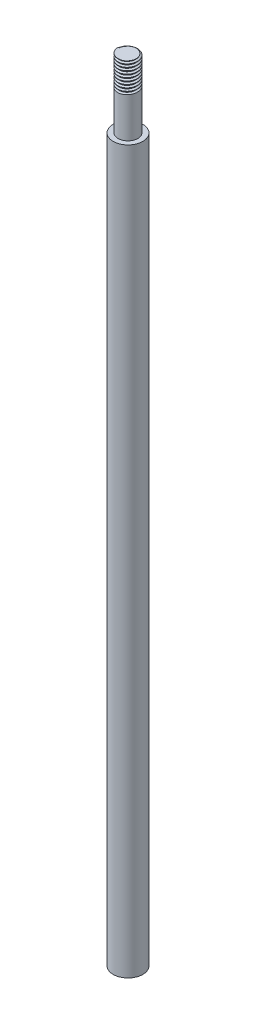
SolidWorks part; units mm, degrees
material "6061-T6 (SS)"
ref_plane "Front Plane" through (0, 0, 0) normal (0, 0, 1) x (1, 0, 0)
ref_plane "Top Plane" through (0, 0, 0) normal (0, 1, 0) x (1, 0, 0)
ref_plane "Right Plane" through (0, 0, 0) normal (1, 0, 0) x (0, 0, -1)
sketch "Sketch1" plane through (0, 0, 0) normal (0, 1, 0) x (1, 0, 0)
  circle A0 centre (0, 0) radius 5
extrude "Boss-Extrude1" add sketch "Sketch1" along normal blind 35
sketch "Sketch2" plane through (0, 0, 0) normal (0, -1, 0) x (1, 0, 0)
  line L0 (5, 0) -> (0, 0)
  circle A0 centre (0, 0) radius 5 construction
  circle A1 centre (0, 0) radius 7.5
  circle M1 centre (0, 0) radius 5
extrude "Boss-Extrude2" add sketch "Sketch2" along normal blind 365 contours A1 M1 | M1 region at (-7.2879, 0, 0) region at (-4.8586, 0, 0)
thread "Thread2" pitch 1.5 method cut trim with start face yes profile "Thread Profile3" start angle 0, offset 1, length 15, pitch 1.5, diameter 10
ref_plane "Plane3" through (-5, 36, 0) normal (0, 0, 1) x (-1, 0, 0)
sketch "Thread Profile3" plane through (-5, 36, 0) normal (0, 0, 1) x (-1, 0, 0)
  line L0 (0, 0) -> (0, 1.5) construction
  line L11 (0, 0) -> (0, 1.3125)
  line L12 (0, 1.3125) -> (-0.8119, 0.8437)
  line L13 (-0.8119, 0.8437) -> (-0.8119, 0.4687)
  line L15 (-0.8119, 0.4687) -> (0, 0)
  line L17 (-0.8119, 0.6562) -> (0, 0.6562) construction
  point P2 (0, 0)
  dimension "Pitch" = 1.5
  dimension "Profile_Angle" = 60
  dimension "Profile_Land" = 0.375
  dimension "Profile_Height" = 0.8119
